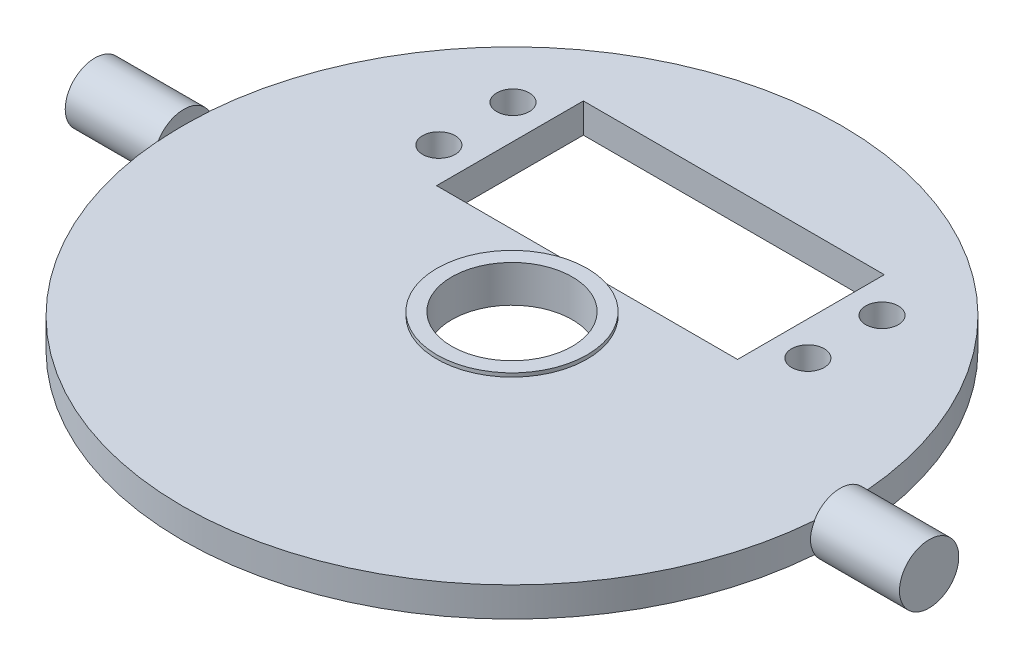
SolidWorks part; units mm, degrees
ref_plane "Front Plane" through (0, 0, 0) normal (0, 0, 1) x (1, 0, 0)
ref_plane "Top Plane" through (0, 0, 0) normal (0, 1, 0) x (1, 0, 0)
ref_plane "Right Plane" through (0, 0, 0) normal (1, 0, 0) x (0, 0, -1)
sketch "Sketch1" plane through (0, 0, 0) normal (0, 1, 0) x (1, 0, 0)
  line L0 (-76.4354, 0) -> (76.4354, 0) construction
  line L1 (-56.2697, 4) -> (-56.2697, -4)
  line L2 (0, 44.45) -> (0, -44.45) construction
  line L3 (-56.2697, 4) -> (-44.2697, 4)
  line L4 (-56.2697, -4) -> (-44.2697, -4)
  line L5 (56.2697, -4) -> (44.2697, -4)
  line L6 (56.2697, 4) -> (56.2697, -4)
  line L7 (56.2697, 4) -> (44.2697, 4)
  line L8 (-56.2697, 0) -> (-44.45, 0)
  line L9 (56.2697, 0) -> (44.45, 0)
  circle A0 centre (0, 0) radius 44.45
  circle A1 centre (0, 0) radius 8.125
  circle A2 centre (0, 0) radius 10.125
  point P6 (0, 0)
  point P9 (-56.2697, 0)
  dimension "D1" = 88.9
  dimension "D4" = 16.25
  dimension "D2" = 8
  dimension "D3" = 12
  dimension "D5" = 2
extrude "Boss-Extrude1" add sketch "Sketch1" along normal mid plane 4 contours A0 L1 region at (0, 0, -43.1928)
revolve "Revolve1" add sketch "Sketch1<6>" angle 360 about L0 region at (-50.3297, 0, 2.0051) region at (50.3297, 0, 2.0051)
sketch "Sketch1<6>" plane through (0, 0, 0) normal (0, 1, 0) x (1, 0, 0) same geometry as "Sketch1"
extrude "Boss-Extrude2" add sketch "Sketch1<7>" along normal mid plane 5 contours A2 A1 region at (-9.8386, 0, 0)
sketch "Sketch1<7>" plane through (0, 0, 0) normal (0, 1, 0) x (1, 0, 0) same geometry as "Sketch1"
sketch "Sketch2" plane through (0, 2, 0) normal (0, 1, 0) x (1, 0, 0)
  line L1 (-20.3, 10.125) -> (20.3, 10.125)
  line L2 (-20.3, 10.125) -> (-20.3, 29.925)
  line L3 (-20.3, 29.925) -> (20.3, 29.925)
  line L4 (20.3, 10.125) -> (20.3, 29.925)
  line L5 (-20.3, 10.125) -> (20.3, 29.925) construction
  line L6 (-20.3, 29.925) -> (20.3, 10.125) construction
  point P0 (0, 20.025)
extrude "Cut-Extrude1" cut sketch "Sketch2" against normal through all
sketch "Sketch3" plane through (0, -2, 0) normal (0, -1, 0) x (1, 0, 0)
  circle A0 centre (24.8896, -15.025) radius 2.2
  arc A1 (26.7, -13.775) -> (26.7, -16.275) centre (24.8896, -15.025) ccw construction
  circle A2 centre (24.8896, -25.025) radius 2.2
  circle A3 centre (-24.8896, -15.025) radius 2.2
  arc A4 (-26.7, -16.275) -> (-26.7, -13.775) centre (-24.8896, -15.025) ccw construction
  arc A5 (26.7, -23.775) -> (26.7, -26.275) centre (24.8896, -25.025) ccw construction
  circle A6 centre (-24.8896, -25.025) radius 2.2
  arc A7 (-26.7, -26.275) -> (-26.7, -23.775) centre (-24.8896, -25.025) ccw construction
extrude "Cut-Extrude2" cut sketch "Sketch3" against normal through all and the other way through all
